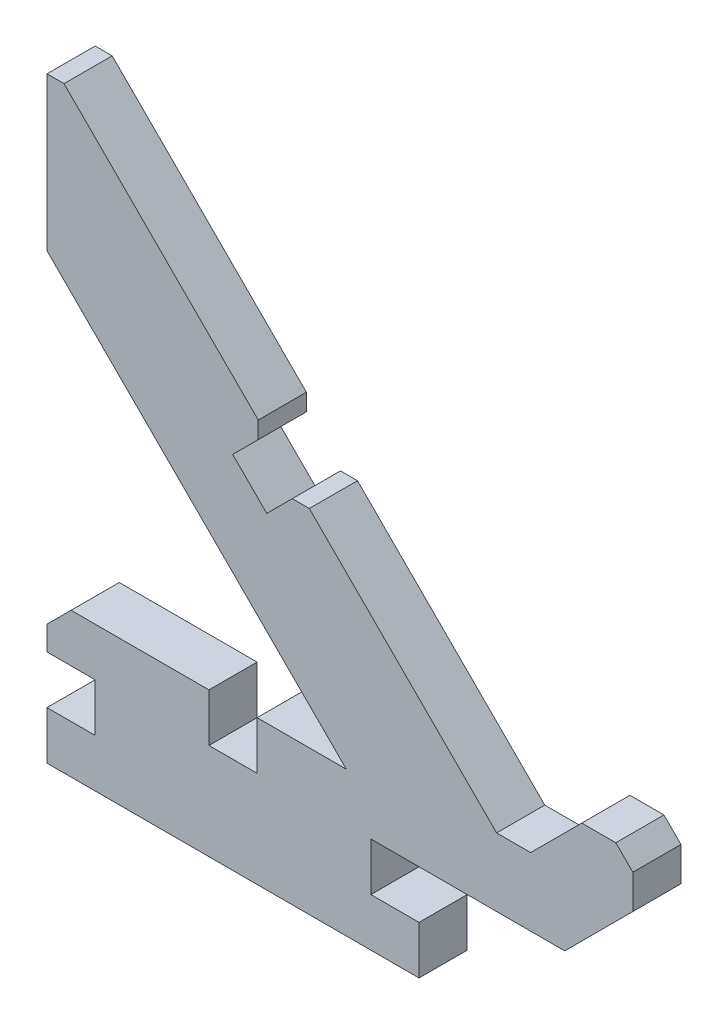
SolidWorks part; units mm, degrees
material "Oak"
ref_plane "Front Plane" through (0, 0, 0) normal (0, 0, 1) x (1, 0, 0)
ref_plane "Top Plane" through (0, 0, 0) normal (0, 1, 0) x (1, 0, 0)
ref_plane "Right Plane" through (0, 0, 0) normal (1, 0, 0) x (0, 0, -1)
sketch "Sketch1" plane through (0, 0, 0) normal (0, 0, 1) x (1, 0, 0)
  line L0 (0, 0) -> (0, 4)
  line L1 (0, 4) -> (4, 4)
  line L2 (4, 4) -> (4, 8)
  line L3 (4, 8) -> (0, 8)
  line L4 (0, 8) -> (0, 51)
  line L5 (0, 51) -> (43, 8)
  line L6 (43, 8) -> (26.9, 8)
  line L7 (26.9, 8) -> (26.9, 4)
  line L8 (26.9, 4) -> (30.9, 4)
  line L9 (30.9, 4) -> (30.9, 0)
  line L10 (30.9, 0) -> (0, 0)
  line L11 (0, 8) -> (0, 4) construction
  line L12 (43, 8) -> (50.0711, 15.0711)
  line L19 (50.0711, 15.0711) -> (45.8284, 19.3137)
  line L20 (45.8284, 19.3137) -> (38.7574, 12.2426)
  line L21 (38.7574, 12.2426) -> (43, 8)
  line L26 (18.2513, 32.7487) -> (15.4228, 29.9203)
  line L27 (15.4228, 29.9203) -> (18.2513, 27.0919)
  line L28 (18.2513, 27.0919) -> (21.0797, 29.9203)
  line L29 (21.0797, 29.9203) -> (18.2513, 32.7487)
  line L38 (0, 36.8579) -> (24.8579, 12)
  line L39 (24.8579, 12) -> (0, 12)
  line L40 (0, 12) -> (0, 36.8579)
  line L47 (13.45, 16) -> (17.45, 16)
  line L50 (20.8579, 12) -> (24.8579, 12)
  line L52 (13.45, 16) -> (13.45, 8)
  line L53 (13.45, 8) -> (17.45, 8)
  line L54 (17.45, 16) -> (17.45, 8)
  point P10 (0, 6)
  point P17 (4, 6)
  point P18 (26.9, 6)
  point P20 (46.5355, 11.5355)
  point P34 (15.45, 16)
  point P39 (13.45, 12)
  point P40 (15.45, 0)
  dimension "D1" = 30.9
  dimension "D2" = 4
  dimension "D3" = 4
  dimension "D4" = 43
  dimension "D5" = 4
  dimension "D6" = 4
  dimension "D7" = 4
  dimension "D8" = 45
  dimension "D11" = 6
  dimension "D12" = 10
  dimension "D13" = 10
  dimension "D14" = 35
  dimension "D17" = 4
  dimension "D18" = 4
  dimension "D19" = 8
  dimension "D22" = 4
extrude "Boss-Extrude1" add sketch "Sketch1" along normal blind 4 contours L39 L54 L53 L52 L4 L3 L2 L1 L0 L10 L9 L8 L7 L6 L5 L28 L27 L26 L38 | L19 L20 L5 L12 region at (0.6671, 2, 0) region at (44.4142, 13.6569, 0)
chamfer "Chamfer1" distance 2 angle 45 5 edges at (50.0711, 15.0711, 2) (45.8284, 19.3137, 2) (38.7574, 12.2426, 2) (0, 12, 2) (0, 51, 2) first distance on face at (46.5355, 11.5355, 2) first distance on face at (47.9497, 17.1924, 2) first distance on face at (42.2929, 15.7782, 2) first distance on face at (6.725, 12, 2) first distance on face at (9.1256, 41.8744, 2)
chamfer "Chamfer2" distance 1 angle 45 2 edges at (18.2513, 32.7487, 2) (21.0797, 29.9203, 2)
